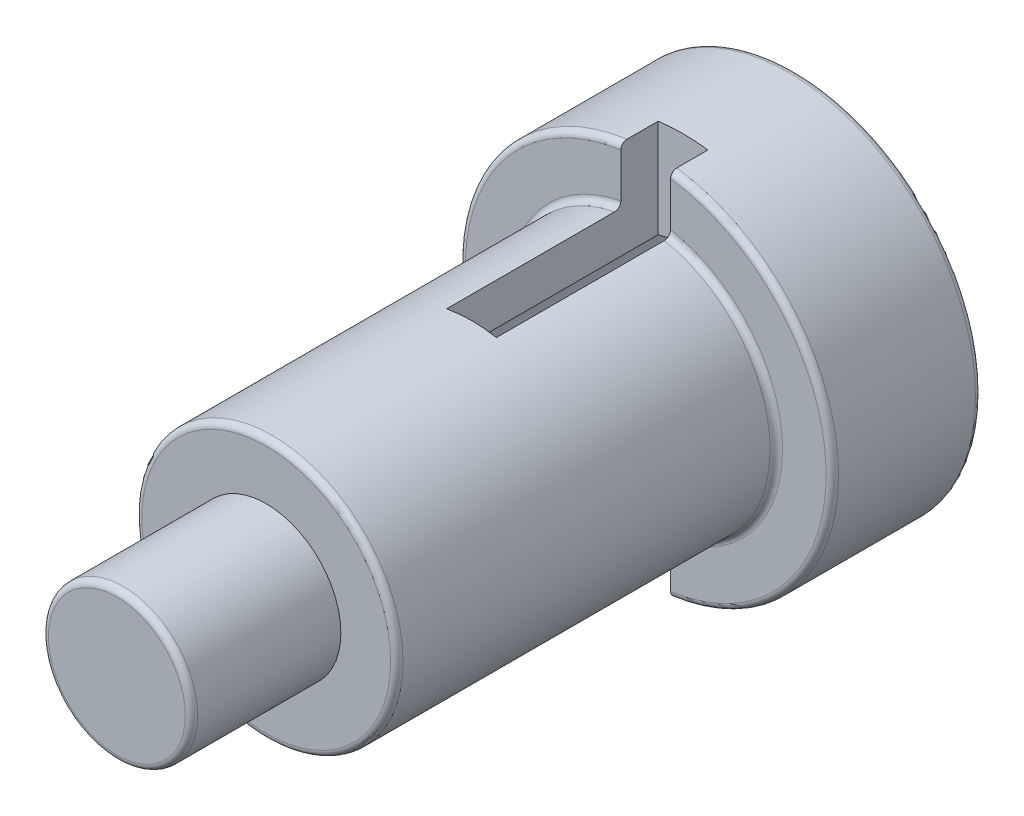
SolidWorks part; units mm, degrees
ref_plane "Front Plane" through (0, 0, 0) normal (0, 0, 1) x (1, 0, 0)
ref_plane "Top Plane" through (0, 0, 0) normal (0, 1, 0) x (1, 0, 0)
ref_plane "Right Plane" through (0, 0, 0) normal (1, 0, 0) x (0, 0, -1)
sketch "Sketch1" plane through (0, 0, 0) normal (0, 0, 1) x (1, 0, 0)
  circle A0 centre (0, 0) radius 30
  circle A1 centre (0, 0) radius 21
  circle A2 centre (0, 0) radius 12
  dimension "D1" = 60
  dimension "D2" = 42
  dimension "D3" = 24
extrude "Boss-Extrude1" add sketch "Sketch1" against normal blind 24 contours A0 A1 | A1 A2 | A2 region at (-29.1515, 0, 0) region at (-20.406, 0, 0) region at (0, 0, 0)
extrude "Boss-Extrude2" add sketch "Sketch1<3>" along normal blind 61 contours A1 A2 | A2 region at (-20.406, 0, 0) region at (0, 0, 0)
sketch "Sketch1<3>" plane through (0, 0, 0) normal (0, 0, 1) x (1, 0, 0) same geometry as "Sketch1"
extrude "Boss-Extrude3" add sketch "Sketch1<4>" along normal blind 24 from surface contours A2 starting at face at (21, 0, 61)
sketch "Sketch1<4>" plane through (0, 0, 0) normal (0, 0, 1) x (1, 0, 0) same geometry as "Sketch1"
sketch "Sketch2" plane through (0, 0, -24) normal (0, 0, -1) x (-1, 0, 0)
  circle A0 centre (0, 0) radius 14.5
  dimension "D1" = 29
extrude "Cut-Extrude1" cut sketch "Sketch2" against normal blind 70
sketch "Sketch3" plane through (0, 0, 0) normal (0, 1, 0) x (1, 0, 0)
  line L0 (-12, -61) -> (12, -61) construction
  line L1 (-4, 6) -> (4, 6)
  line L2 (-4, 6) -> (-4, -28)
  line L3 (-4, -28) -> (4, -28)
  line L4 (4, 6) -> (4, -28)
  point P4 (0, 6)
  dimension "D1" = 8
  dimension "D2" = 33
  dimension "D3" = 34
extrude "Cut-Extrude2" cut sketch "Sketch3" against normal through all both and the other way through all contours L2 L1 L4 L3
fillet "Fillet1" radius 1 7 edges at (-30, 0, 0) (30, 0, 0) (30, 0, -24) (-21, 0, 0) (21, 0, 0) (21, 0, 61) (12, 0, 85)
